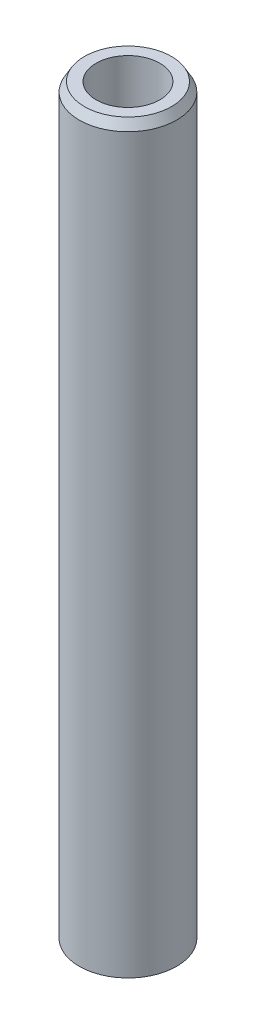
SolidWorks part; units mm, degrees
ref_plane "Front Plane" through (0, 0, 0) normal (0, 0, 1) x (1, 0, 0)
ref_plane "Top Plane" through (0, 0, 0) normal (0, 1, 0) x (1, 0, 0)
ref_plane "Right Plane" through (0, 0, 0) normal (1, 0, 0) x (0, 0, -1)
sketch "Sketch1" plane through (0, 0, 0) normal (0, 1, 0) x (1, 0, 0)
  circle A0 centre (0, 0) radius 17.5
  dimension "SHAFT_OD" = 35
extrude "Boss-Extrude1" add sketch "Sketch1" along normal blind 268.2857
sketch "Sketch2" plane through (0, 0, 0) normal (0, 1, 0) x (1, 0, 0)
  circle A0 centre (0, 0) radius 11.4236
  dimension "BORE_D" = 22.8473
extrude "Cut-Extrude1" cut sketch "Sketch2" along normal through all
chamfer "Chamfer1" distance 3.2479 angle 30 2 edges at (0, 268.2857, 17.5) (0, 0, 17.5) first distance on face at (0, 268.2857, 17.5) first distance on face at (0, 0, 11.4236)
